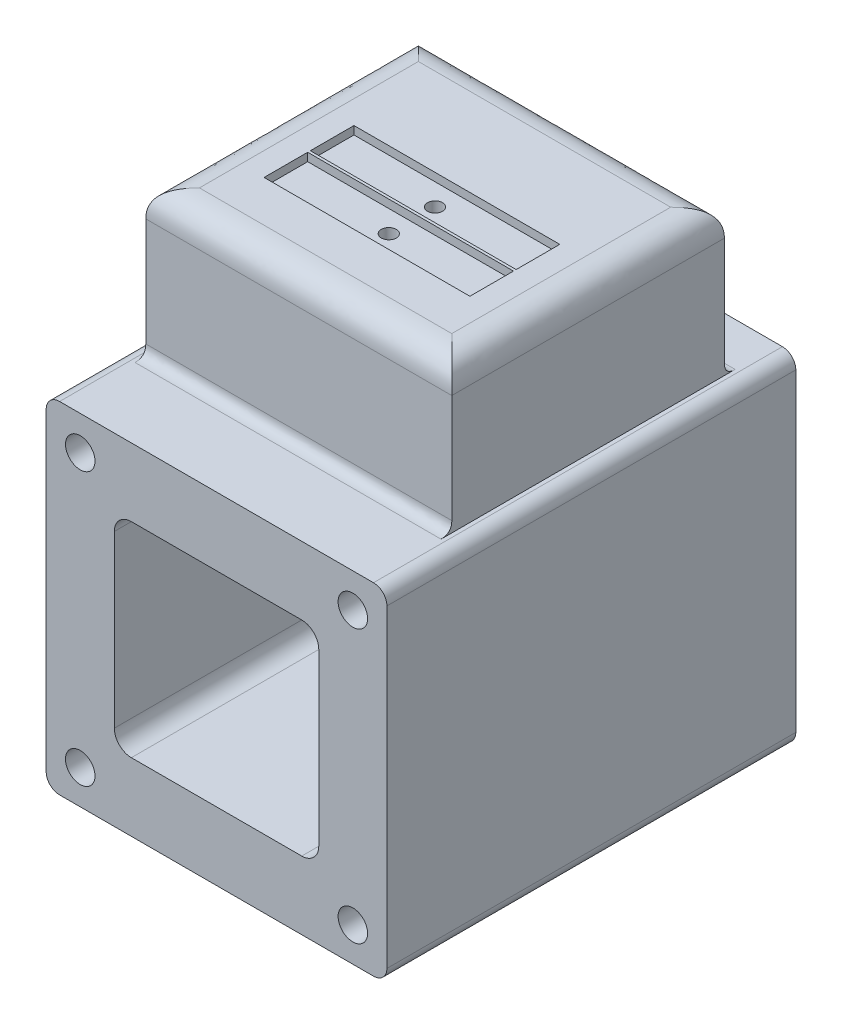
SolidWorks part; units mm, degrees
material "PETG"
ref_plane "Front Plane" through (0, 0, 0) normal (0, 0, 1) x (1, 0, 0)
ref_plane "Top Plane" through (0, 0, 0) normal (0, 1, 0) x (1, 0, 0)
ref_plane "Right Plane" through (0, 0, 0) normal (1, 0, 0) x (0, 0, -1)
sketch "Sketch1" plane through (0, 0, 0) normal (0, 0, 1) x (1, 0, 0)
  line L1 (-31.75, -31.75) -> (31.75, -31.75)
  line L2 (-31.75, -31.75) -> (-31.75, 31.75)
  line L3 (-31.75, 31.75) -> (31.75, 31.75)
  line L4 (31.75, -31.75) -> (31.75, 31.75)
  line L5 (-31.75, -31.75) -> (31.75, 31.75) construction
  line L6 (-31.75, 31.75) -> (31.75, -31.75) construction
  point P0 (0, 0)
  dimension "D1" = 63.5
  dimension "D2" = 63.5
extrude "Boss-Extrude1" add sketch "Sketch1" along normal blind 76.2
sketch "Sketch2" plane through (0, 0, 76.2) normal (0, 0, 1) x (1, 0, 0)
  line L1 (-25.4, -25.4) -> (25.4, -25.4)
  line L2 (-25.4, -25.4) -> (-25.4, 25.4)
  line L3 (-25.4, 25.4) -> (25.4, 25.4)
  line L4 (25.4, -25.4) -> (25.4, 25.4)
  line L5 (-25.4, -25.4) -> (25.4, 25.4) construction
  line L6 (-25.4, 25.4) -> (25.4, -25.4) construction
  point P1 (0, 0)
  point P2 (25.4, 25.4)
  point P3 (-25.4, -25.4)
  point P4 (-25.4, 25.4)
  point P5 (25.4, -25.4)
  dimension "D1" = 50.8
  dimension "D2" = 50.8
hole_wizard "M5 Clearance Hole1" positions "Sketch2" profile "Sketch3" hole size "M5" standard "ANSI Metric"
sketch "Sketch3" plane through (25.4, -25.4, 76.2) normal (1, 0, 0) x (0, -1, 0)
  line L0 (0, 0) -> (0, 76.2)
  line L1 (0, 76.2) -> (2.75, 76.2)
  line L2 (2.75, 76.2) -> (2.75, 0)
  line L5 (2.75, 0) -> (0, 0)
  line L11 (0, -6.35) -> (0, 107.95) construction
  dimension "Thru Hole Dia." = 5.5
  dimension "Thru Hole Depth" = 76.2
sketch "Sketch4" plane through (0, 0, 0) normal (0, 0, -1) x (-1, 0, 0)
  line L1 (19.05, -19.05) -> (-19.05, -19.05)
  line L2 (19.05, -19.05) -> (19.05, 19.05)
  line L3 (19.05, 19.05) -> (-19.05, 19.05)
  line L4 (-19.05, -19.05) -> (-19.05, 19.05)
  line L5 (19.05, -19.05) -> (-19.05, 19.05) construction
  line L6 (19.05, 19.05) -> (-19.05, -19.05) construction
  point P0 (0, 0)
  dimension "D1" = 38.1
  dimension "D2" = 38.1
extrude "Cut-Extrude1" cut sketch "Sketch4" against normal through all
fillet "Fillet1" radius 2.5 4 edges at (31.75, -31.75, 38.1) (-31.75, -31.75, 38.1) (-31.75, 31.75, 38.1) (31.75, 31.75, 38.1)
fillet "Fillet2" radius 3.175 4 edges at (19.05, -19.05, 38.1) (-19.05, -19.05, 38.1) (-19.05, 19.05, 38.1) (19.05, 19.05, 38.1)
sketch "Sketch5" plane through (0, 31.75, 0) normal (0, 1, 0) x (1, 0, 0)
  line L0 (0, 0) -> (0, -60.8776) construction
  line L2 (28.5137, -60.8776) -> (-28.5137, -60.8776)
  line L3 (28.5137, -60.8776) -> (28.5137, -10.0776)
  line L4 (28.5137, -10.0776) -> (-28.5137, -10.0776)
  line L5 (-28.5137, -60.8776) -> (-28.5137, -10.0776)
  line L6 (28.5137, -60.8776) -> (-28.5137, -10.0776) construction
  line L7 (28.5137, -10.0776) -> (-28.5137, -60.8776) construction
  line L9 (-29.25, -60.8776) -> (29.25, -60.8776) construction
  line L10 (-29.25, 0) -> (-29.25, -76.2) construction
  line L11 (29.25, -76.2) -> (29.25, 0) construction
  point P3 (0, -35.4776)
  point P8 (0, -25.3757)
  dimension "D1" = 50.8
  dimension "D2" = 57.0274
extrude "Boss-Extrude2" add sketch "Sketch5" along normal blind 27.178
sketch "Sketch7" plane through (0, 58.928, 0) normal (0, 1, 0) x (1, 0, 0)
  line L0 (0, -10.0776) -> (0, -60.8776) construction
  line L1 (28.5137, -10.0776) -> (-28.5137, -10.0776) construction
  line L2 (-28.5137, -60.8776) -> (28.5137, -60.8776) construction
  line L3 (-28.5137, -35.4776) -> (28.5137, -35.4776) construction
  line L4 (-28.5137, -10.0776) -> (-28.5137, -60.8776) construction
  line L5 (28.5137, -60.8776) -> (28.5137, -10.0776) construction
  line L6 (-255.6194, 99.0745) -> (-293.9734, 99.0745)
  line L7 (19.177, -39.5416) -> (-19.177, -39.5416)
  line L8 (19.177, -39.5416) -> (19.177, -31.4136)
  line L9 (19.177, -31.4136) -> (-19.177, -31.4136)
  line L10 (-19.177, -39.5416) -> (-19.177, -31.4136)
  line L11 (19.177, -39.5416) -> (-19.177, -31.4136) construction
  line L12 (19.177, -31.4136) -> (-19.177, -39.5416) construction
  line L13 (-255.6194, 99.0745) -> (-255.6194, 107.2025)
  line L14 (-255.6194, 107.2025) -> (-293.9734, 107.2025)
  line L15 (-293.9734, 99.0745) -> (-293.9734, 107.2025)
  line L16 (-255.6194, 99.0745) -> (-293.9734, 107.2025) construction
  line L17 (-255.6194, 107.2025) -> (-293.9734, 99.0745) construction
  line L19 (19.177, -48.1653) -> (-19.177, -48.1653)
  line L20 (19.177, -48.1653) -> (19.177, -40.0373)
  line L21 (19.177, -40.0373) -> (-19.177, -40.0373)
  line L22 (-19.177, -48.1653) -> (-19.177, -40.0373)
  line L23 (19.177, -48.1653) -> (-19.177, -40.0373) construction
  line L24 (19.177, -40.0373) -> (-19.177, -48.1653) construction
  point P12 (0, -35.4776)
  point P17 (-274.7964, 103.1385)
  point P22 (0, -44.1013)
  dimension "D1" = 38.354
  dimension "D2" = 8.128
  dimension "D3" = 38.354
  dimension "D4" = 8.128
extrude "Cut-Extrude2" cut sketch "Sketch7" against normal blind 1.524
sketch "Sketch8" plane through (0, 57.404, 0) normal (0, 1, 0) x (1, 0, 0)
  line L0 (0, -31.4136) -> (0, -39.5416) construction
  line L1 (19.177, -31.4136) -> (-19.177, -31.4136) construction
  line L2 (-19.177, -39.5416) -> (19.177, -39.5416) construction
  line L3 (-19.177, -35.4776) -> (19.177, -35.4776) construction
  line L4 (-19.177, -31.4136) -> (-19.177, -39.5416) construction
  line L5 (19.177, -39.5416) -> (19.177, -31.4136) construction
  line L7 (0, -40.0373) -> (0, -48.1653) construction
  line L8 (19.177, -40.0373) -> (-19.177, -40.0373) construction
  line L9 (-19.177, -48.1653) -> (19.177, -48.1653) construction
  line L11 (-19.177, -44.1013) -> (19.177, -44.1013) construction
  line L12 (-19.177, -40.0373) -> (-19.177, -48.1653) construction
  line L13 (19.177, -48.1653) -> (19.177, -40.0373) construction
  circle A0 centre (0, -35.4776) radius 1.4
  point P12 (0, -35.4776)
  point P37 (0, -44.1013)
  dimension "D1" = 2.8
hole_wizard "M3 Clearance Hole1" positions "Sketch8" profile "Sketch9" hole size "M3" standard "ANSI Metric" end condition up to next
sketch "Sketch9" plane through (0, 57.404, 44.1013) normal (1, 0, 0) x (0, 0, 1)
  line L0 (0, 0) -> (0, 38.354)
  line L1 (0, 38.354) -> (1.4, 38.354)
  line L2 (1.4, 38.354) -> (1.4, 0)
  line L5 (1.4, 0) -> (0, 0)
  line L11 (0, -6.35) -> (0, 107.95) construction
  dimension "Thru Hole Dia." = 2.8
  dimension "Thru Hole Depth" = 38.354
fillet "Fillet3" radius 5 4 edges at (0, 58.928, 10.0776) (0, 58.928, 60.8776) (28.5137, 58.928, 35.4776) (-28.5137, 58.928, 35.4776) conic rho 0.5
fillet "Fillet4" radius 2 1 edges at (0, 31.75, 60.8776) conic rho 0.5
fillet "Fillet5" radius 2 1 edges at (0, 31.75, 10.0776) conic rho 0.5
